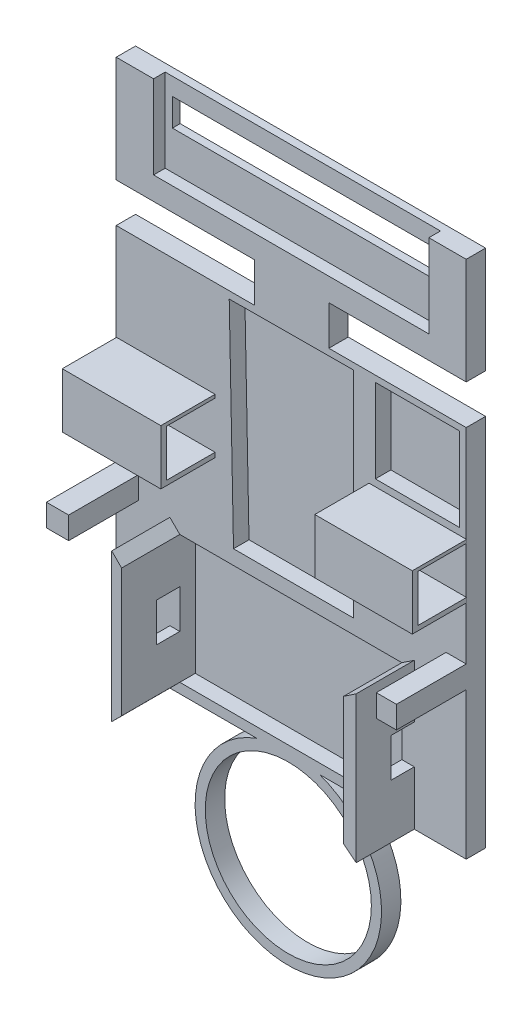
SolidWorks part; units mm, degrees
other "seguidor_linha"
ref_plane "Plano frontal" through (0, 0, 0) normal (0, 0, 1) x (1, 0, 0)
ref_plane "Plano superior" through (0, 0, 0) normal (0, 1, 0) x (1, 0, 0)
ref_plane "Plano direito" through (0, 0, 0) normal (1, 0, 0) x (0, 0, -1)
sketch "Esboço1" plane through (0, 0, 0) normal (0, 0, 1) x (1, 0, 0)
  line L0 (-44.6735, 40.7151) -> (-44.6735, 19.6036)
  line L1 (-44.6735, 40.7151) -> (45.616, 40.7151)
  line L2 (45.616, 40.7151) -> (45.616, 19.6036)
  line L3 (-44.6735, 19.6036) -> (-9.0478, 19.6036)
  line L4 (45.616, 19.6036) -> (10.1788, 19.6036)
  line L5 (10.1788, 19.6036) -> (10.1788, 9.4248)
  line L6 (-9.0478, 19.6036) -> (-9.0478, 9.4248)
  line L7 (-9.0478, 9.4248) -> (-44.6735, 9.4248)
  line L8 (10.1788, 9.4248) -> (45.616, 9.4248)
  line L9 (-44.6735, 9.4248) -> (-44.6735, -71.4399)
  line L10 (-44.6735, -71.4399) -> (45.616, -71.4399)
  line L11 (45.616, -71.4399) -> (45.616, 9.4248)
extrude "base_seguidor" add sketch "Esboço1" along normal blind 5
other "resize_base" face at (0.4712, -71.4399, 2.5) offset 10.7189 parameters "D1"=10.7189
other "resize_base_2" face at (0.4712, 40.7151, 2.5) offset 6.3042 parameters "D1"=6.3042
other "Mover face10" face at (0.4712, -82.1588, 2.5) face at (0.4712, -82.1588, 2.5) offset 4.846 parameters "D1"=4.846
sketch "Esboço27" plane through (0, 0, 5) normal (0, 0, 1) x (1, 0, 0)
  line L0 (-44.6735, -43.3942) -> (-38.9375, -43.3942)
  line L1 (-44.6735, 9.4248) -> (-44.6735, -87.0048) construction
  line L2 (-38.9375, -43.3942) -> (-38.9375, -49.1356)
  line L3 (-38.9375, -49.1356) -> (-44.6735, -49.1356)
  line L4 (-44.6735, -49.1356) -> (-44.6735, -43.3942)
  line L5 (40.4251, -43.3942) -> (45.616, -43.3942)
  line L6 (45.616, -87.0048) -> (45.616, 9.4248) construction
  line L7 (45.616, -43.3942) -> (45.616, -49.1356)
  line L8 (45.616, -49.1356) -> (40.4251, -49.1356)
  line L9 (40.4251, -49.1356) -> (40.4251, -43.3942)
extrude "base_engerenagem" add sketch "Esboço27" along normal blind 18
sketch "Esboço18" plane through (0, 0, 5) normal (0, 0, 1) x (1, 0, 0)
  circle A1 centre (-0.2746, -109.6385) radius 24.0465
  circle A2 centre (-0.2746, -109.6385) radius 21.4231
extrude "Ressalto-extrusão11" add sketch "Esboço18" against normal blind 5
sketch "Esboço22" plane through (0, 0, 5) normal (0, 0, 1) x (1, 0, 0)
  line L0 (-28.2709, -51.4001) -> (-28.2709, -84.4284)
  line L2 (29.0183, -84.4284) -> (29.0183, -51.4001)
  line L3 (29.0183, -51.4001) -> (-28.2709, -51.4001)
  line L4 (-28.2709, -84.4284) -> (29.0183, -84.4284)
extrude "Corte-extrusão2" cut sketch "Esboço22" against normal blind 4
sketch "Esboço24" plane through (0, 0, 5) normal (0, 0, 1) x (1, 0, 0)
  line L0 (-28.2709, -51.4001) -> (-30.8237, -48.8473)
  line L1 (29.0183, -51.4001) -> (32.2142, -49.2696)
  line L2 (29.0183, -84.4284) -> (29.0183, -51.4001) construction
  line L3 (29.0183, -51.4001) -> (-28.2709, -51.4001) construction
  line L4 (29.0183, -84.4284) -> (32.2142, -87.0048)
  line L5 (29.0183, -84.4284) -> (29.0183, -51.4001)
  line L6 (7.8465, -87.0048) -> (45.616, -87.0048) construction
  line L7 (32.2142, -49.2696) -> (32.2142, -87.0048)
  line L8 (-30.8237, -48.8473) -> (-30.8237, -87.0048)
  line L9 (-44.6735, -87.0048) -> (-8.3956, -87.0048) construction
  line L10 (-30.8237, -87.0048) -> (-28.2709, -84.4284)
  line L11 (-28.2709, -51.4001) -> (-28.2709, -84.4284)
extrude "Ressalto-extrusão12" add sketch "Esboço24" along normal blind 15
sketch "Esboço26" plane through (32.2142, 0, 0) normal (1, 0, 0) x (0, 0, -1)
  line L0 (-10.9821, -63.0629) -> (-10.9821, -73.0655)
  line L1 (-5, -73.0655) -> (-5, -63.0629)
  line L4 (-5, -87.0048) -> (-5, -49.1356) construction
  line L5 (-5, -63.0629) -> (-10.9821, -63.0629)
  line L6 (-10.9821, -73.0655) -> (-5, -73.0655)
extrude "Corte-extrusão3" cut sketch "Esboço26" against normal blind 64
sketch "Esboço6" plane through (0, 0, 5) normal (0, 0, 1) x (1, 0, 0)
  line L0 (45.7054, -29.6821) -> (20.5567, -29.6821)
  line L6 (-19.1599, -29.6821) -> (-19.1599, -15.5282)
  line L10 (20.5567, -29.6821) -> (20.5567, -15.5282)
  line L11 (20.5567, -15.5282) -> (45.7054, -15.5282)
  line L12 (45.7054, -29.6821) -> (45.7054, -15.5282)
  line L13 (-19.1599, -15.5282) -> (-44.584, -15.5282)
  line L15 (-44.584, -15.5282) -> (-44.584, -29.6821)
  line L16 (-44.584, -29.6821) -> (-19.1599, -29.6821)
extrude "Ressalto-extrusão10" add sketch "Esboço6" along normal blind 14 contours L13 L15 L16 L6 | L11 L12 L0 L10
sketch "Esboço19" plane through (-44.6735, 0, 0) normal (-1, 0, 0) x (0, 0, 1)
  line L0 (17.586, -28.4784) -> (17.586, -16.3914)
  line L2 (17.586, -16.3914) -> (5, -16.3914)
  line L6 (5, 9.4248) -> (5, -43.3942) construction
  line L7 (5, -16.3914) -> (5, -28.4784)
  line L8 (5, -15.5282) -> (5, -29.6821) construction
  line L9 (5, -28.4784) -> (17.586, -28.4784)
extrude "Corte-extrusão1" cut sketch "Esboço19" against normal blind 92 contours L0 L2 L7 L9
sketch "Esboço4" plane through (0, 0, 5) normal (0, 0, 1) x (1, 0, 0)
  line L0 (-15.5168, 7.5731) -> (16.486, 7.7415)
  line L8 (22.1752, -13.7622) -> (22.1752, 7.8052)
  line L12 (22.1752, 7.8052) -> (43.8646, 7.8052)
  line L14 (43.8646, 7.8052) -> (43.8646, -13.7622)
  line L18 (-14.4125, -47.6648) -> (16.486, -47.6648)
  line L19 (16.486, -47.6648) -> (16.486, 7.7415)
  line L20 (-14.4125, -47.6648) -> (-15.5168, 7.5731)
  line L21 (22.1752, -13.7622) -> (43.8646, -13.7622)
extrude "pcb_buracos" cut sketch "Esboço4" against normal blind 4 contours L14 L21 L8 L12 | L19 L0 L20 L18
sketch "Esboço2" plane through (0, 0, 5) normal (0, 0, 1) x (1, 0, 0)
  line L0 (-35.0374, 25.5264) -> (35.9799, 25.5264)
  line L1 (45.616, 47.0192) -> (-44.6735, 47.0192) construction
  line L2 (-35.0374, 47.0192) -> (35.9799, 47.0192)
  line L4 (35.9799, 25.5264) -> (35.9799, 47.0192)
  line L5 (-35.0374, 25.5264) -> (-35.0374, 47.0192)
extrude "sensor_infra_encaixe" cut sketch "Esboço2" against normal blind 3
sketch "Esboço9" plane through (0, 0, 2) normal (0, 0, 1) x (1, 0, 0)
  line L5 (-33.1653, 35.4307) -> (-33.1653, 42.5131)
  line L6 (-33.1653, 42.5131) -> (33.9891, 42.5131)
  line L7 (-33.1653, 35.4307) -> (33.9891, 35.4307)
  line L8 (33.9891, 42.5131) -> (33.9891, 35.4307)
extrude "furo_sensor" cut sketch "Esboço9" against normal blind 10
